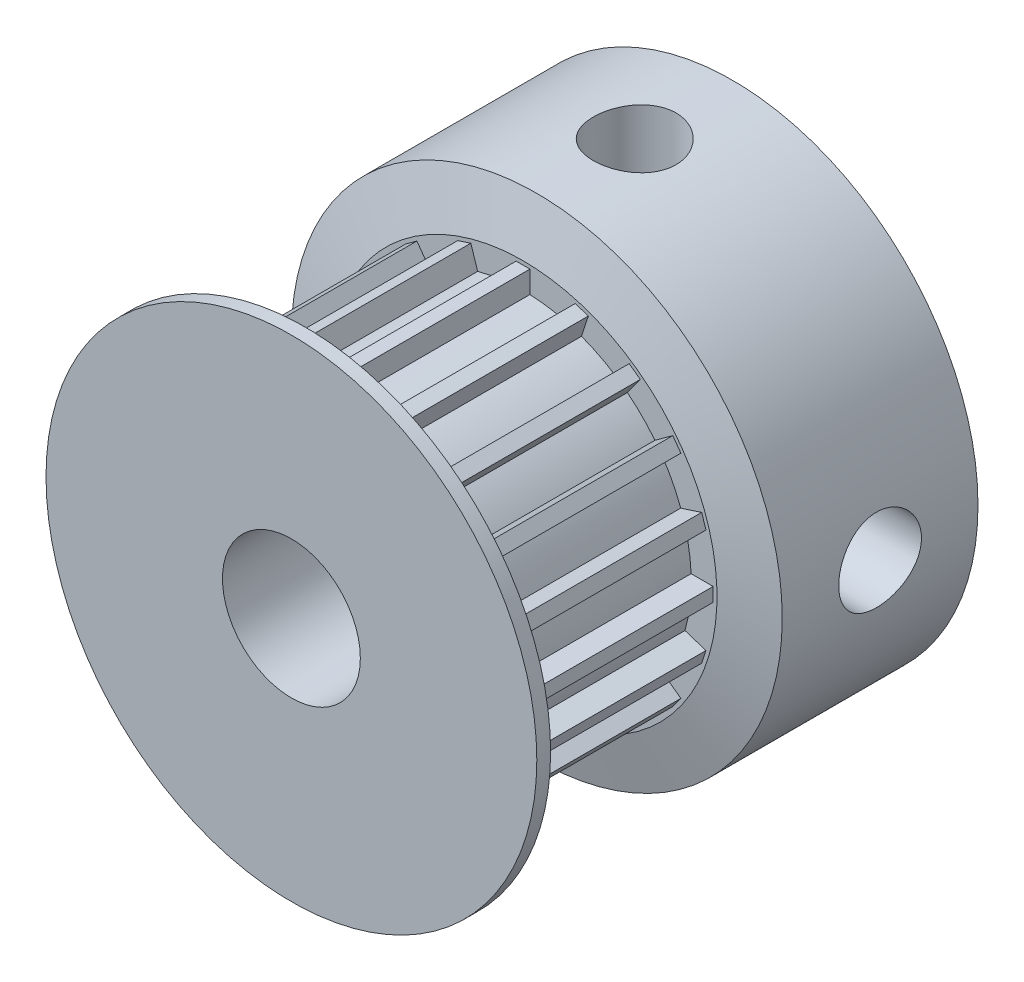
SolidWorks part; units mm, degrees
ref_plane "Front Plane" through (0, 0, 0) normal (0, 0, 1) x (1, 0, 0)
ref_plane "Top Plane" through (0, 0, 0) normal (0, 1, 0) x (1, 0, 0)
ref_plane "Right Plane" through (0, 0, 0) normal (1, 0, 0) x (0, 0, -1)
sketch "Sketch2" plane through (0, 0, 0) normal (1, 0, 0) x (0, 0, -1)
  line L0 (-16, 2.5) -> (0, 2.5)
  line L1 (0, 2.5) -> (0, 8.9)
  line L2 (0, 8.9) -> (-7.6, 8.9)
  line L3 (-7.6, 8.9) -> (-7.6, 6.1)
  line L4 (-7.6, 6.1) -> (-15, 6.1)
  line L5 (-15, 6.1) -> (-15, 8.9)
  line L6 (-15, 8.9) -> (-16, 8.9)
  line L7 (-16, 8.9) -> (-16, 2.5)
  line L8 (-79.6095, 0) -> (75.5553, 0) construction
  dimension "D1" = 16
  dimension "D2" = 8.9
  dimension "D3" = 1
  dimension "D4" = 7.4
  dimension "D5" = 2.5
  dimension "D6" = 6.1
revolve "Revolve1" add sketch "Sketch2" angle 360 about L8
chamfer "Chamfer1" distance 0.5 angle 75 1 edges at (8.9, 0, 15) first distance on face at (8.9, 0, 16)
chamfer "Chamfer2" distance 0.5 angle 75 1 edges at (8.9, 0, 7.6) first distance on face at (8.9, 0, 7.6)
sketch "Sketch4" plane through (0, 0, 7.6) normal (0, 0, 1) x (1, 0, 0)
  line L0 (1.6457, 5.8738) -> (1.8929, 6.6347)
  line L1 (1.8929, 6.6347) -> (2.3684, 6.4802)
  line L2 (-0.25, 6.0949) -> (-0.25, 6.8949)
  line L3 (-0.25, 6.8949) -> (0.25, 6.8949)
  line L4 (0.25, 6.0949) -> (0.25, 6.8949)
  line L5 (2.1212, 5.7193) -> (2.3684, 6.4802)
  line L6 (3.3802, 5.0778) -> (3.8505, 5.725)
  line L7 (3.8505, 5.725) -> (4.255, 5.4311)
  line L8 (3.7847, 4.7839) -> (4.255, 5.4311)
  line L9 (4.7839, 3.7847) -> (5.4311, 4.255)
  line L10 (5.4311, 4.255) -> (5.725, 3.8505)
  line L11 (5.0778, 3.3802) -> (5.725, 3.8505)
  line L12 (5.7193, 2.1212) -> (6.4802, 2.3684)
  line L13 (6.4802, 2.3684) -> (6.6347, 1.8929)
  line L14 (5.8738, 1.6457) -> (6.6347, 1.8929)
  line L15 (6.0949, 0.25) -> (6.8949, 0.25)
  line L16 (6.8949, 0.25) -> (6.8949, -0.25)
  line L17 (6.0949, -0.25) -> (6.8949, -0.25)
  line L18 (5.8738, -1.6457) -> (6.6347, -1.8929)
  line L19 (6.6347, -1.8929) -> (6.4802, -2.3684)
  line L20 (5.7193, -2.1212) -> (6.4802, -2.3684)
  line L21 (5.0778, -3.3802) -> (5.725, -3.8505)
  line L22 (5.725, -3.8505) -> (5.4311, -4.255)
  line L23 (4.7839, -3.7847) -> (5.4311, -4.255)
  line L24 (3.7847, -4.7839) -> (4.255, -5.4311)
  line L25 (4.255, -5.4311) -> (3.8505, -5.725)
  line L26 (3.3802, -5.0778) -> (3.8505, -5.725)
  line L27 (2.1212, -5.7193) -> (2.3684, -6.4802)
  line L28 (2.3684, -6.4802) -> (1.8929, -6.6347)
  line L29 (1.6457, -5.8738) -> (1.8929, -6.6347)
  line L30 (0.25, -6.0949) -> (0.25, -6.8949)
  line L31 (0.25, -6.8949) -> (-0.25, -6.8949)
  line L32 (-0.25, -6.0949) -> (-0.25, -6.8949)
  line L33 (-1.6457, -5.8738) -> (-1.8929, -6.6347)
  line L34 (-1.8929, -6.6347) -> (-2.3684, -6.4802)
  line L35 (-2.1212, -5.7193) -> (-2.3684, -6.4802)
  line L36 (-3.3802, -5.0778) -> (-3.8505, -5.725)
  line L37 (-3.8505, -5.725) -> (-4.255, -5.4311)
  line L38 (-3.7847, -4.7839) -> (-4.255, -5.4311)
  line L39 (-4.7839, -3.7847) -> (-5.4311, -4.255)
  line L40 (-5.4311, -4.255) -> (-5.725, -3.8505)
  line L41 (-5.0778, -3.3802) -> (-5.725, -3.8505)
  line L42 (-5.7193, -2.1212) -> (-6.4802, -2.3684)
  line L43 (-6.4802, -2.3684) -> (-6.6347, -1.8929)
  line L44 (-5.8738, -1.6457) -> (-6.6347, -1.8929)
  line L45 (-6.0949, -0.25) -> (-6.8949, -0.25)
  line L46 (-6.8949, -0.25) -> (-6.8949, 0.25)
  line L47 (-6.0949, 0.25) -> (-6.8949, 0.25)
  line L48 (-5.8738, 1.6457) -> (-6.6347, 1.8929)
  line L49 (-6.6347, 1.8929) -> (-6.4802, 2.3684)
  line L50 (-5.7193, 2.1212) -> (-6.4802, 2.3684)
  line L51 (-5.0778, 3.3802) -> (-5.725, 3.8505)
  line L52 (-5.725, 3.8505) -> (-5.4311, 4.255)
  line L53 (-4.7839, 3.7847) -> (-5.4311, 4.255)
  line L54 (-3.7847, 4.7839) -> (-4.255, 5.4311)
  line L55 (-4.255, 5.4311) -> (-3.8505, 5.725)
  line L56 (-3.3802, 5.0778) -> (-3.8505, 5.725)
  line L57 (-2.1212, 5.7193) -> (-2.3684, 6.4802)
  line L58 (-2.3684, 6.4802) -> (-1.8929, 6.6347)
  line L59 (-1.6457, 5.8738) -> (-1.8929, 6.6347)
  arc A0 (-3.3802, 5.0778) -> (-3.7847, 4.7839) centre (0, 0) ccw
  arc A1 (-1.6457, 5.8738) -> (-2.1212, 5.7193) centre (0, 0) ccw
  arc A2 (0.25, 6.0949) -> (-0.25, 6.0949) centre (0, 0) ccw
  arc A3 (2.1212, 5.7193) -> (1.6457, 5.8738) centre (0, 0) ccw
  arc A4 (3.7847, 4.7839) -> (3.3802, 5.0778) centre (0, 0) ccw
  arc A5 (5.0778, 3.3802) -> (4.7839, 3.7847) centre (0, 0) ccw
  arc A6 (5.8738, 1.6457) -> (5.7193, 2.1212) centre (0, 0) ccw
  arc A7 (6.0949, -0.25) -> (6.0949, 0.25) centre (0, 0) ccw
  arc A8 (5.7193, -2.1212) -> (5.8738, -1.6457) centre (0, 0) ccw
  arc A9 (4.7839, -3.7847) -> (5.0778, -3.3802) centre (0, 0) ccw
  arc A10 (3.3802, -5.0778) -> (3.7847, -4.7839) centre (0, 0) ccw
  arc A11 (1.6457, -5.8738) -> (2.1212, -5.7193) centre (0, 0) ccw
  arc A12 (-0.25, -6.0949) -> (0.25, -6.0949) centre (0, 0) ccw
  arc A13 (-2.1212, -5.7193) -> (-1.6457, -5.8738) centre (0, 0) ccw
  arc A14 (-3.7847, -4.7839) -> (-3.3802, -5.0778) centre (0, 0) ccw
  arc A15 (-5.0778, -3.3802) -> (-4.7839, -3.7847) centre (0, 0) ccw
  arc A16 (-5.8738, -1.6457) -> (-5.7193, -2.1212) centre (0, 0) ccw
  arc A17 (-6.0949, 0.25) -> (-6.0949, -0.25) centre (0, 0) ccw
  arc A18 (-5.7193, 2.1212) -> (-5.8738, 1.6457) centre (0, 0) ccw
  arc A19 (-4.7839, 3.7847) -> (-5.0778, 3.3802) centre (0, 0) ccw
  dimension "D1" = 12.2
  dimension "D2" = 0.5
  dimension "D3" = 0.25
  dimension "D4" = 0.8
  dimension "D5" = 20
extrude "Boss-Extrude1" add sketch "Sketch4" along normal up to surface (7.4 mm away) up to face at (7.034, 0, 15)
ref_plane "Plane1" through (0, 8.9, 0) normal (0, 1, 0) x (-1, 0, 0)
sketch "Sketch6" plane through (0, 8.9, 0) normal (0, 1, 0) x (-1, 0, 0)
  line L2 (0, 3.55) -> (4.2063, 3.55) construction
  circle A0 centre (0, 3.55) radius 1.5
  dimension "D1" = 3
  dimension "D2" = 3.55
extrude "Cut-Extrude1" cut sketch "Sketch6" against normal blind 10
pattern_circular "CirPattern1" count 2 every 270 about axis through (0, 0, 0) along (0, 0, 1) of "Cut-Extrude1"
